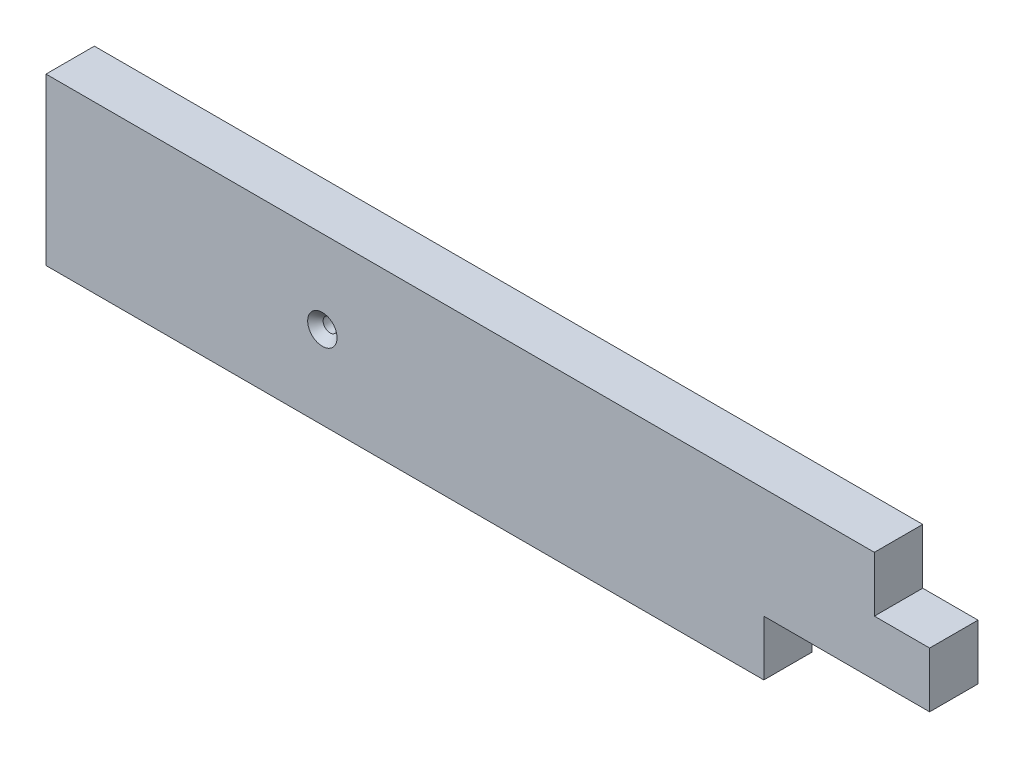
SolidWorks part; units mm, degrees
ref_plane "Front Plane" through (0, 0, 0) normal (0, 0, 1) x (1, 0, 0)
ref_plane "Top Plane" through (0, 0, 0) normal (0, 1, 0) x (1, 0, 0)
ref_plane "Right Plane" through (0, 0, 0) normal (1, 0, 0) x (0, 0, -1)
sketch "Sketch1" plane through (0, 0, 0) normal (0, 1, 0) x (1, 0, 0)
  line L1 (-203.0251, -11.1125) -> (203.0251, -11.1125)
  line L2 (-203.0251, -11.1125) -> (-203.0251, 11.1125)
  line L3 (-203.0251, 11.1125) -> (203.0251, 11.1125)
  line L4 (203.0251, -11.1125) -> (203.0251, 11.1125)
  line L5 (-203.0251, -11.1125) -> (203.0251, 11.1125) construction
  line L6 (-203.0251, 11.1125) -> (203.0251, -11.1125) construction
  point P0 (0, 0)
extrude "Boss-Extrude1" add sketch "Sketch1" along normal mid plane 76.2 contours L1 L4 L3 L2
sketch "Sketch3" plane through (0, 0, 11.1125) normal (0, 0, 1) x (1, 0, 0)
  line L1 (203.0251, 38.1) -> (177.6251, 38.1)
  line L2 (203.0251, 38.1) -> (203.0251, 12.7)
  line L3 (203.0251, 12.7) -> (177.6251, 12.7)
  line L4 (177.6251, 38.1) -> (177.6251, 12.7)
  line L5 (126.8386, -12.7) -> (203.0251, -12.7)
  line L6 (126.8386, -12.7) -> (126.8386, -38.1)
  line L7 (126.8386, -38.1) -> (203.0251, -38.1)
  line L8 (203.0251, -12.7) -> (203.0251, -38.1)
extrude "Cut-Extrude1" cut sketch "Sketch3" against normal through all
sketch "Sketch4" plane through (0, 0, 11.1125) normal (0, 0, 1) x (1, 0, 0)
  line L0 (-203.0251, 38.1) -> (-76.0251, 38.1)
  line L1 (-203.0251, 38.1) -> (177.6251, 38.1) construction
  dimension "D1" = 127
hole_wizard "CSK for M6 Hex Socket Countersunk Head Screw1" positions "Sketch6" profile "Sketch5" countersink size "M6" standard "Lanco STD" end condition through all
sketch "Sketch6" plane through (0, 0, 11.1125) normal (0, 0, 1) x (1, 0, 0)
  point P0 (-76.0251, 0)
sketch "Sketch5" plane through (-76.0251, 0, 11.1125) normal (1, 0, 0) x (0, -1, 0)
  line L0 (0, 0) -> (0, 22.225)
  line L1 (0, 22.225) -> (3.2, 22.225)
  line L2 (3.2, 22.225) -> (3.2, 3.55)
  line L3 (3.2, 3.55) -> (6.75, 0)
  line L5 (6.75, 0) -> (0, 0)
  line L6 (-3.2, 3.55) -> (-6.75, 0) construction
  line L11 (0, -6.35) -> (0, 107.95) construction
  dimension "Thru Hole Dia." = 6.4
  dimension "Thru Hole Depth" = 22.225
  dimension "Near C'Sink Dia." = 13.5
  dimension "Near C'Sink Angle" = 90
